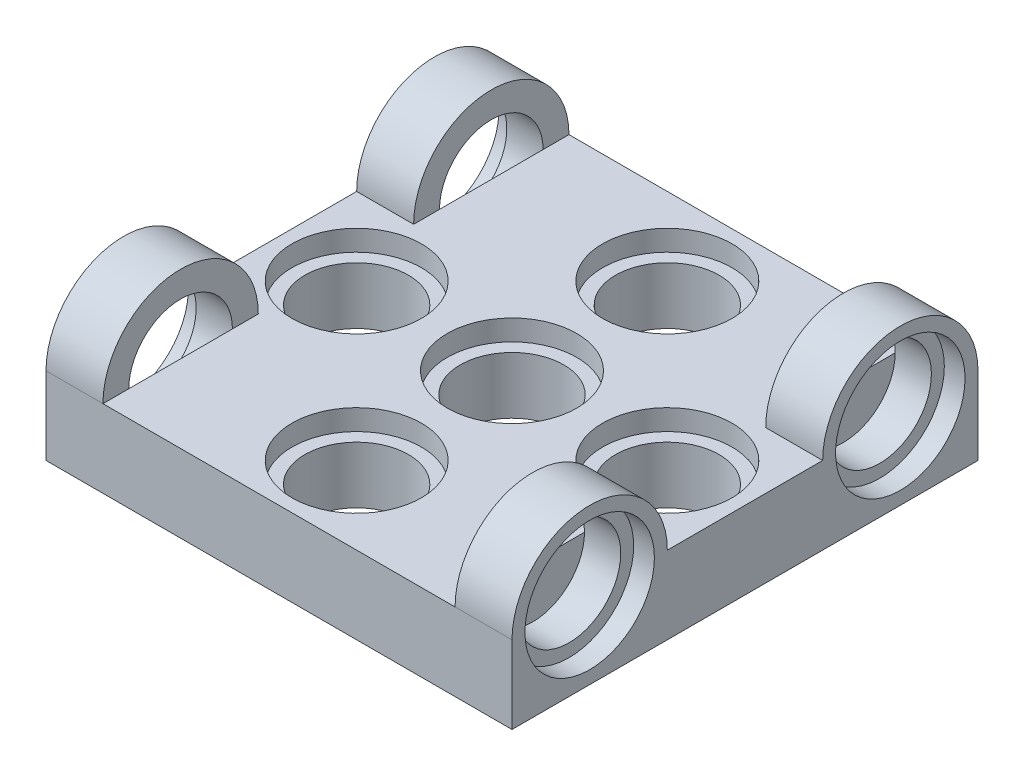
SolidWorks part; units mm, degrees
material "ABS"
ref_plane "Front Plane" through (0, 0, 0) normal (0, 0, 1) x (1, 0, 0)
ref_plane "Top Plane" through (0, 0, 0) normal (0, 1, 0) x (1, 0, 0)
ref_plane "Right Plane" through (0, 0, 0) normal (1, 0, 0) x (0, 0, -1)
sketch "Sketch1" plane through (0, 0, 0) normal (0, 1, 0) x (1, 0, 0)
  line L1 (0, 4.5) -> (9, 4.5)
  line L2 (0, 4.5) -> (0, -4.5)
  line L3 (0, -4.5) -> (9, -4.5)
  line L4 (9, 4.5) -> (9, -4.5)
  dimension "D1" = 9
extrude "Boss-Extrude1" add sketch "Sketch1" against normal blind 3
hole_wizard "Hole1" positions "Sketch4" profile "Sketch5" legacy end condition through all
sketch "Sketch4" plane through (0, 0, 0) normal (0, 1, 0) x (1, 0, 0)
  line L1 (0, -4.5) -> (9, -4.5) construction
  line L2 (9, -4.5) -> (9, 4.5) construction
  point P0 (9, -4.5)
  point P2 (9, 1.5)
  point P4 (3, -4.5)
  dimension "D1" = 6
  dimension "D2" = 6
sketch "Sketch5" plane through (9, 0, 4.5) normal (1, 0, 0) x (0, 0, 1)
  line L0 (0, 0) -> (0, 4.2017)
  line L1 (0, 4.2017) -> (2, 3)
  line L2 (2, 3) -> (2, 0.8)
  line L3 (2, 0.8) -> (2.5, 0.8)
  line L4 (2.5, 0) -> (0, 0)
  line L5 (0, -11.3109) -> (0, 121.1557) construction
  line L6 (0, 4.2017) -> (-2, 3) construction
  line L7 (2.5, 0.8) -> (2.5, 0)
  dimension "Depth" = 3
  dimension "Drill Angle" = 118
  dimension "Diameter" = 4
  dimension "C-Bore Diameter" = 5
  dimension "C-Bore Depth" = 0.8
sketch "Sketch6" plane through (0, 0, 0) normal (1, 0, 0) x (0, 0, -1)
  line L1 (4.5, 0) -> (-4.5, 0) construction
  line L2 (4.5, 0) -> (-1.5, 0)
  arc A0 (4.5, 0) -> (-1.5, 0) centre (1.5, 0) ccw
  dimension "D1" = 6
extrude "Boss-Extrude2" add sketch "Sketch6" along normal blind 2.2
hole_wizard "Hole2" positions "Sketch7" profile "Sketch8" legacy
sketch "Sketch7" plane through (0, 0, 0) normal (-1, 0, 0) x (0, 0, 1)
  arc A0 (1.5, 0) -> (-4.5, 0) centre (-1.5, 0) ccw construction
  point P0 (-1.5, 0)
sketch "Sketch8" plane through (0, 0, -1.5) normal (0, 1, 0) x (0, 0, 1)
  line L0 (0, 0) -> (0, 3.4017)
  line L1 (0, 3.4017) -> (2, 2.2)
  line L2 (2, 2.2) -> (2, 0.8)
  line L3 (2, 0.8) -> (2.5, 0.8)
  line L4 (2.5, 0) -> (0, 0)
  line L5 (0, -11.3109) -> (0, 121.1557) construction
  line L6 (0, 3.4017) -> (-2, 2.2) construction
  line L7 (2.5, 0.8) -> (2.5, 0)
  dimension "Depth" = 2.2
  dimension "Drill Angle" = 118
  dimension "Diameter" = 4
  dimension "C-Bore Diameter" = 5
  dimension "C-Bore Depth" = 0.8
sketch "Sketch11" plane through (0, 0, 0) normal (1, 0, 0) x (0, 0, -1)
  line L0 (-0.5, 0) -> (3.5, 0) construction
  circle A0 centre (1.5, 0) radius 3
  point P5 (1.5, 0)
  dimension "D1" = 6
ref_plane "Plane1" through (0, 0, 4.5) normal (0, 0, 1) x (1, 0, 0)
mirror "Mirror1" about plane through (0, 0, 4.5) normal (0, 0, 1) of "Hole1", "Boss-Extrude1", "Boss-Extrude2", "Hole2"
ref_plane "Plane2" through (9, 0, 0) normal (1, 0, 0) x (0, 0, -1)
mirror "Mirror2" about plane through (9, 0, 0) normal (1, 0, 0) of "Hole1", "Mirror1", "Boss-Extrude1", "Boss-Extrude2", "Hole2"
